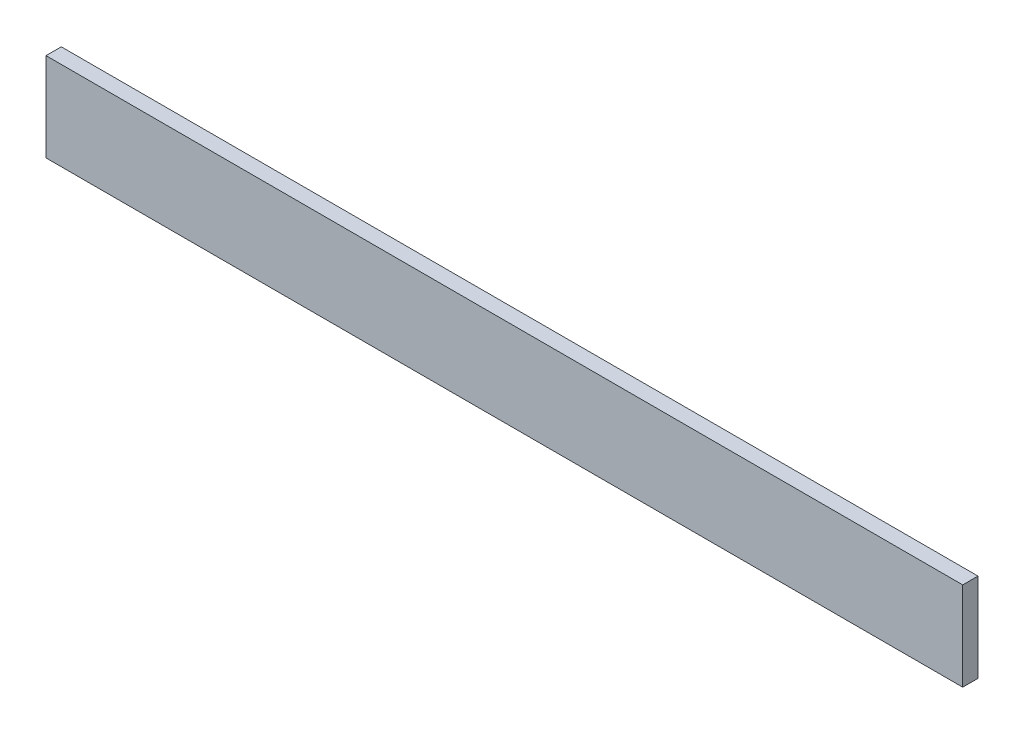
SolidWorks part; units mm, degrees
ref_plane "Plan de face" through (0, 0, 0) normal (0, 0, 1) x (1, 0, 0)
ref_plane "Plan de dessus" through (0, 0, 0) normal (0, 1, 0) x (1, 0, 0)
ref_plane "Plan de droite" through (0, 0, 0) normal (1, 0, 0) x (0, 0, -1)
sketch "Esquisse1" plane through (0, 0, 0) normal (0, 0, 1) x (1, 0, 0)
  line L1 (0, 0) -> (600, 0)
  line L2 (0, 0) -> (0, 58)
  line L3 (0, 58) -> (600, 58)
  line L4 (600, 0) -> (600, 58)
  dimension "D1" = 600
  dimension "D2" = 58
extrude "Boss.-Extru.1" add sketch "Esquisse1" along normal blind 10
